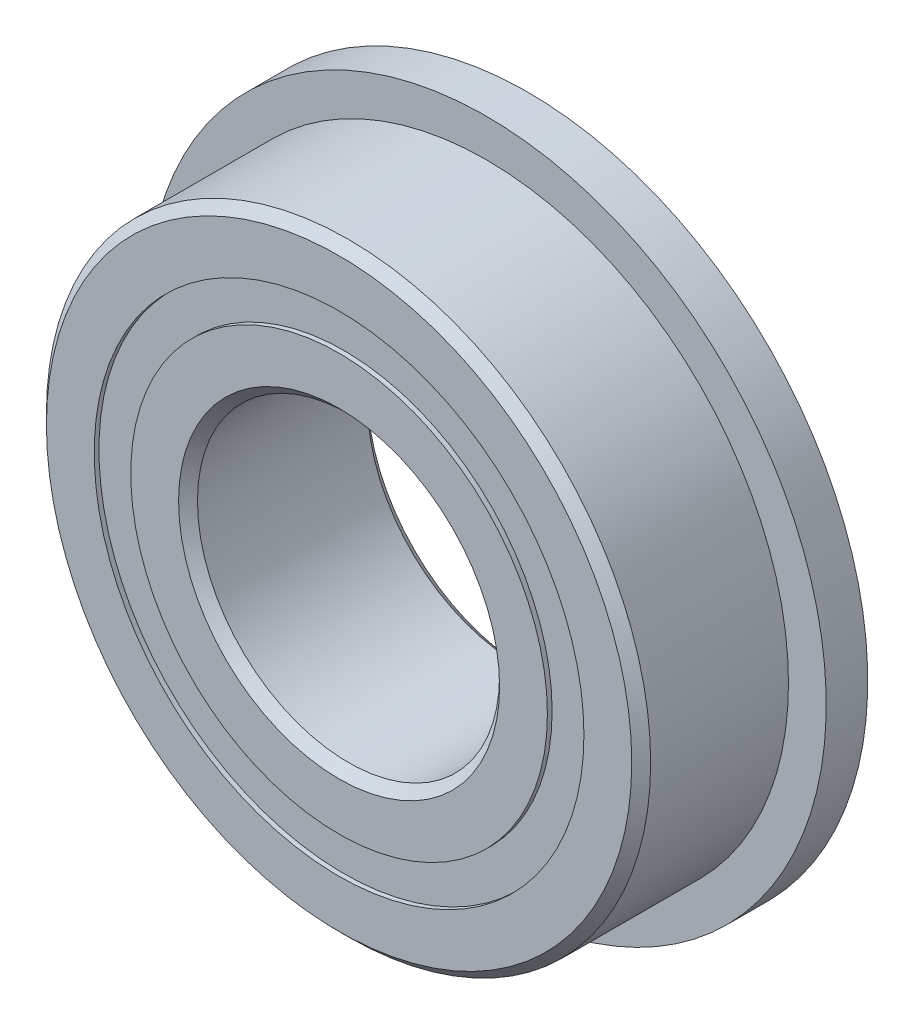
SolidWorks part; units mm, degrees
ref_plane "Front Plane" through (0, 0, 0) normal (0, 0, 1) x (1, 0, 0)
ref_plane "Top Plane" through (0, 0, 0) normal (0, 1, 0) x (1, 0, 0)
ref_plane "Right Plane" through (0, 0, 0) normal (1, 0, 0) x (0, 0, -1)
sketch "Sketch1" plane through (0, 0, 0) normal (1, 0, 0) x (0, 0, -1)
  line L0 (-2.5, 0) -> (2.5, 0) construction
  line L1 (0, 8) -> (0, -8) construction
  line L2 (2.25, 8) -> (-2.25, 8)
  line L3 (-2.25, 8) -> (-2.5, 7.75)
  line L4 (-2.5, 7.75) -> (-2.5, 6.4835)
  line L5 (-2.5, 6.4835) -> (-1.1111, 6.4835)
  line L6 (2.5, 6.4835) -> (1.1111, 6.4835)
  line L7 (2.5, 7.75) -> (2.5, 6.4835)
  line L8 (2.25, 8) -> (2.5, 7.75)
  line L9 (0, 8) -> (0, 6) construction
  line L10 (0, 6) -> (0, 4) construction
  arc A0 (-1.1111, 6.4835) -> (1.1111, 6.4835) centre (0, 6) cw
  point P14 (0, 4)
  dimension "Width" = 5
  dimension "OD" = 16
  dimension "D1" = 45
  dimension "D2" = 0.25
  dimension "Shaft Dia" = 8
  dimension "D3" = 2.2222
  dimension "D4" = 0.4835
revolve "Revolve1" add sketch "Sketch1" angle 360 about L0
sketch "Sketch3" plane through (0, 0, 0) normal (1, 0, 0) x (0, 0, -1)
  line L0 (-2.5, 5.5165) -> (-1.1111, 5.5165)
  line L1 (0, 8) -> (0, -8) construction
  line L2 (-2.5, 7.75) -> (-2.5, 6.4835) construction
  line L3 (-2.5, 5.5165) -> (-2.5, 4.25)
  line L4 (-2.25, 8) -> (-2.5, 7.75) construction
  line L5 (-2.5, 4.25) -> (-2.25, 4)
  line L6 (-2.25, 4) -> (2.25, 4)
  line L7 (2.25, 8) -> (2.25, -8) construction
  line L8 (2.25, 4) -> (2.5, 4.25)
  line L9 (2.5, -7.75) -> (2.5, 7.75) construction
  line L10 (2.5, 4.25) -> (2.5, 5.5165)
  line L11 (2.5, 5.5165) -> (1.1111, 5.5165)
  line L13 (2.25, 8) -> (2.5, 7.75) construction
  arc A0 (1.1111, 6.4835) -> (-1.1111, 6.4835) centre (0, 6) ccw construction
  arc A1 (1.1111, 5.5165) -> (-1.1111, 5.5165) centre (0, 6) cw
revolve "Revolve3" add sketch "Sketch3" angle 360 about L0
sketch "Sketch4" plane through (0, 0, 0) normal (1, 0, 0) x (0, 0, -1)
  line L0 (-1.2118, 6) -> (1.2118, 6)
  arc A2 (-1.2118, 6) -> (1.2118, 6) centre (0, 6) cw
  arc A3 (1.1111, 6.4835) -> (-1.1111, 6.4835) centre (0, 6) ccw construction
revolve "Revolve4" add sketch "Sketch4" angle 360 about L0
ref_axis "Axis1" through (0, 0, -2.5) along (0, 0, 1)
pattern_circular "CirPattern1" count 12 every 30 about axis through (0, 0, -2.5) along (0, 0, 1) of bodies 104
sketch "Sketch5" plane through (0, 0, 0) normal (1, 0, 0) x (0, 0, -1)
  line L0 (-2.5, 6.4835) -> (-1.1111, 6.4835) construction
  line L1 (-2.375, 6.4835) -> (-1.2118, 6.4835)
  line L2 (-2.375, 6.4835) -> (-2.375, 5.5165)
  line L3 (-2.375, 5.5165) -> (-1.2118, 5.5165)
  line L4 (-1.2118, 6.4835) -> (-1.2118, 5.5165)
  line L5 (-2.5, 5.5165) -> (-1.1111, 5.5165) construction
  line L6 (2.5, 6.4835) -> (1.1111, 6.4835) construction
  line L7 (2.375, 6.4835) -> (1.2118, 6.4835)
  line L8 (2.375, 6.4835) -> (2.375, 5.5165)
  line L9 (2.375, 5.5165) -> (1.2118, 5.5165)
  line L10 (1.2118, 6.4835) -> (1.2118, 5.5165)
  line L11 (2.5, 5.5165) -> (1.1111, 5.5165) construction
  line L12 (-2.25, 8) -> (-2.5, 7.75) construction
  point P18 (-2.375, 7.875)
revolve "Revolve5" add sketch "Sketch5" angle 360 about L0
sketch "Sketch6" plane through (0, 0, 0) normal (1, 0, 0) x (0, 0, -1)
  line L0 (2.5, 0) -> (-2.5, 0) construction
  line L1 (2.5, 6.4835) -> (1.4, 6.4835)
  line L2 (2.5, 6.4835) -> (2.5, 9)
  line L3 (2.5, 9) -> (1.4, 9)
  line L4 (1.4, 6.4835) -> (1.4, 9)
  dimension "Th" = 1.1
  dimension "Flange OD" = 18
revolve "Revolve6" add sketch "Sketch6" angle 360 about L0
equation "\"D2@Sketch1\" = \"Width@Sketch1\"*.05"
equation "\"D3@Sketch1\" = \"Width@Sketch1\"/2.25"
equation "\"D4@Sketch1\" = (((\"OD@Sketch1\"-\"Width@Sketch1\")/2)/3.25)/3.5"
equation "\"D2@CirPattern1\" = 360/\"Balls@CirPattern1\""
